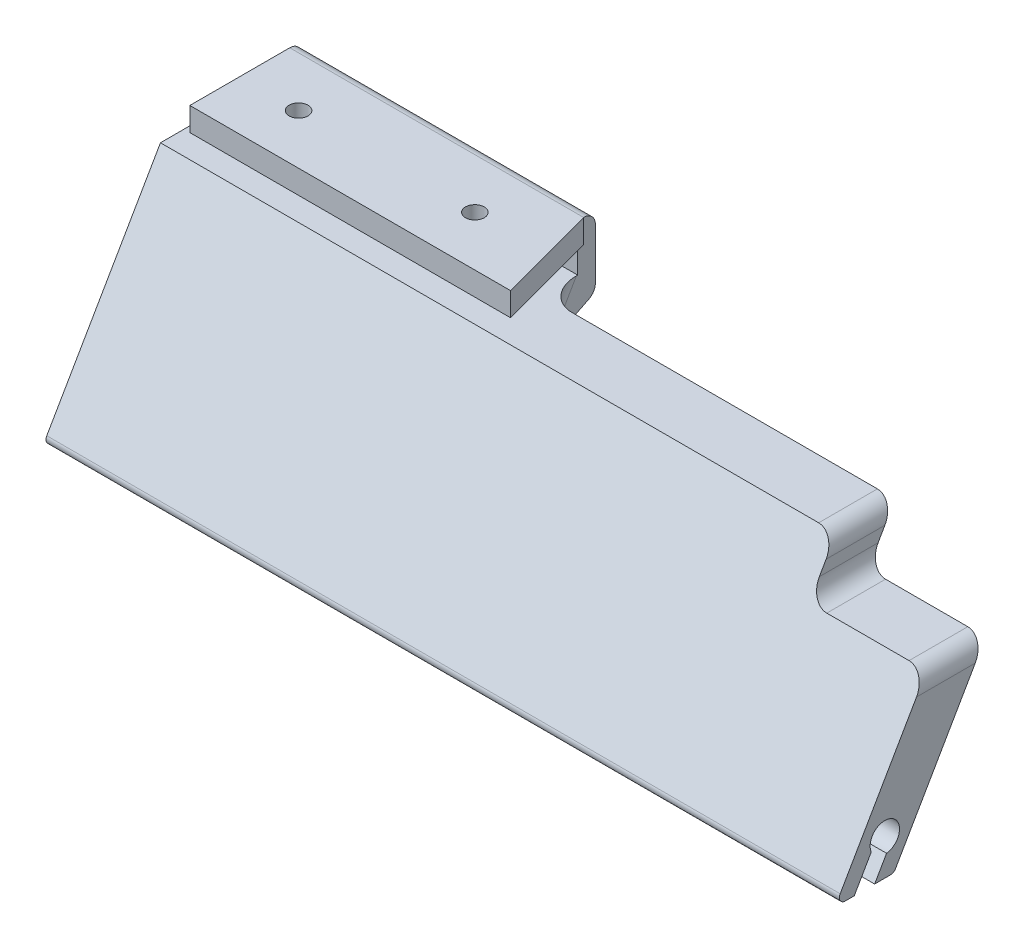
SolidWorks part; units mm, degrees
ref_plane "Front Plane" through (0, 0, 0) normal (0, 0, 1) x (1, 0, 0)
ref_plane "Top Plane" through (0, 0, 0) normal (0, 1, 0) x (1, 0, 0)
ref_plane "Right Plane" through (0, 0, 0) normal (1, 0, 0) x (0, 0, -1)
sketch "Sketch2" plane through (0, 0, 0) normal (1, 0, 0) x (0, 0, -1)
  line L0 (0, 0) -> (20.2073, 35)
  line L1 (20.2073, 35) -> (30.2073, 35)
  line L2 (30.2073, 35) -> (10, 0)
  line L3 (10, 0) -> (0, 0)
  line L4 (0, 0) -> (0, 35) construction
  line L5 (25.2073, 35) -> (5, 0) construction
  line L6 (3.2679, 0) -> (7.1651, 6.75)
  line L7 (7.1651, 6.75) -> (9.7631, 5.25)
  line L8 (9.7631, 5.25) -> (6.7321, 0)
  line L34 (20.2073, 35) -> (39.2073, 35)
  line L35 (20.2073, 35) -> (20.2073, 31)
  line L36 (20.2073, 31) -> (39.2073, 31)
  line L37 (39.2073, 35) -> (39.2073, 31)
  line L38 (39.2073, 35) -> (36.2073, 35)
  line L39 (39.2073, 35) -> (39.2073, 39)
  line L40 (39.2073, 39) -> (36.2073, 39)
  line L41 (36.2073, 35) -> (36.2073, 39)
  line L42 (39.2073, 39) -> (20.2073, 39)
  line L43 (39.2073, 39) -> (39.2073, 43)
  line L44 (39.2073, 43) -> (20.2073, 43)
  line L45 (20.2073, 39) -> (20.2073, 43)
  circle A0 centre (8.4641, 6) radius 2.5
  point P14 (8.4641, 6)
  dimension "D5" = 5
  dimension "D1" = 30
  dimension "D2" = 10
  dimension "D3" = 35
  dimension "D4" = 3
  dimension "D6" = 6
  dimension "D7" = 4
  dimension "D8" = 4
  dimension "D9" = 3
  dimension "D10" = 6
extrude "Boss-Extrude2" add sketch "Sketch2" along normal blind 50 contours L45 L42 L40 L43 L44 | L41 L34 L39 L40 | L37 L34 L2 L36 | L35 L36 L2 L1 | A0 L8 L3 L2 L36 L35 L0 L6 region at (0, 17.0999, -14.8085) region at (0, 33.087, -24.655) region at (0, 32.9242, -34.108) region at (0, 37, -37.7073) region at (0, 41, -29.7073)
sketch "Sketch3" plane through (50, 0, 0) normal (1, 0, 0) x (0, 0, -1)
  line L0 (0, 0) -> (20.2073, 35)
  line L2 (20.2073, 35) -> (30.2073, 35)
  line L3 (30.2073, 35) -> (10, 0)
  line L4 (10, 0) -> (6.7321, 0)
  line L5 (6.7321, 0) -> (8.7631, 3.5179)
  line L6 (8.7631, 3.5179) -> (6.1651, 5.0179)
  line L7 (6.1651, 5.0179) -> (3.2679, 0)
  line L8 (3.2679, 0) -> (0, 0)
  line L9 (20.2073, 35) -> (36.2073, 35) construction
  line L10 (0, 0) -> (20.2073, 35) construction
  circle A0 centre (8.4641, 6) radius 2.5
  arc A1 (8.7631, 3.5179) -> (6.1651, 5.0179) centre (8.4641, 6) ccw construction
  line M14 (20.2073, 35) -> (0, 0)
  line M15 (0, 0) -> (3.2679, 0)
  line M16 (3.2679, 0) -> (6.1651, 5.0179)
  arc M17 (6.1651, 5.0179) -> (8.7631, 3.5179) centre (8.4641, 6) cw
  line M18 (8.7631, 3.5179) -> (6.7321, 0)
  line M19 (6.7321, 0) -> (10, 0)
  line M20 (10, 0) -> (27.8979, 31)
extrude "Boss-Extrude3" add sketch "Sketch3" along normal blind 5 and the other way blind 130 contours L2 M14 M15 M16 M17 M18 M19 M20 region at (50, 18.8865, -15.9088)
fillet "Fillet5" radius 50 1 edges at (25, 31, -27.8979)
fillet "Fillet6" radius 5 2 edges at (0, 22.5778, -23.0353) (50, 22.5778, -23.0353)
fillet "Fillet7" radius 2 2 edges at (25, 43, -39.2073) (25, 31, -39.2073)
fillet "Fillet8" radius 1 2 edges at (-12.5, 0, -10) (-12.5, 0, 0)
ref_plane "Plane1" through (-80, 0, 0) normal (-1, 0, 0) x (0, 0, 1)
mirror "Mirror6" about plane through (-80, 0, 0) normal (-1, 0, 0) of bodies 103
sketch "Sketch4" plane through (0, 0, 0) normal (0, 1, 0) x (1, 0, 0)
  line L0 (-80, 55) -> (-80, -55) construction
  line L1 (-80, 0.7321) -> (55, 0.7321)
  line L2 (-80, 0.7321) -> (-80, 39.2073)
  line L3 (-80, 39.2073) -> (55, 39.2073)
  line L4 (55, 0.7321) -> (55, 39.2073)
  line L5 (55, 20.2073) -> (55, 0.866) construction
  line L7 (-215, 0.7321) -> (55, 0.7321) construction
  line L8 (0, 39.2073) -> (50, 39.2073) construction
extrude "Cut-Extrude2" cut sketch "Sketch4" along normal through all
sketch "Sketch5" plane through (0, 43, 0) normal (0, 1, 0) x (1, 0, 0)
  line L0 (-160, 37.2073) -> (-155.4449, 20.2073)
  line L1 (-155.4449, 20.2073) -> (-160, 20.2073)
  line L2 (-160, 20.2073) -> (-160, 37.2073)
  line L3 (-210, 20.2073) -> (-160, 20.2073) construction
  dimension "D1" = 15
extrude "Boss-Extrude4" add sketch "Sketch5" against normal up to surface (4 mm away)
sketch "Sketch6" plane through (0, 43, 0) normal (0, 1, 0) x (1, 0, 0)
  line L0 (-210, 28.7073) -> (-157.7224, 28.7073) construction
  line L1 (-210, 37.2073) -> (-210, 20.2073) construction
  line L2 (-155.4449, 20.2073) -> (-160, 37.2073) construction
  circle A0 centre (-200, 28.7073) radius 1.6
  circle A1 centre (-170, 28.7073) radius 1.6
  dimension "D1" = 3.2
  dimension "D3" = 10
  dimension "D2" = 10
extrude "Cut-Extrude3" cut sketch "Sketch6" against normal through all
ref_plane "Plane2" through (0, 32, 0) normal (0, 1, 0) x (1, 0, 0)
sketch "Sketch7" plane through (0, 32, 0) normal (0, 1, 0) x (1, 0, 0)
  circle A0 centre (-200, 28.7073) radius 3.5
  circle A1 centre (-170, 28.7073) radius 3.5
  dimension "D1" = 7
extrude "Cut-Extrude4" cut sketch "Sketch7" against normal through all
sketch "Sketch8" plane through (0, 0, -39.2073) normal (0, 0, -1) x (-1, 0, 0)
  line L1 (80, 35) -> (100, 35)
  line L2 (80, 35) -> (80, 27)
  line L3 (80, 27) -> (100, 27)
  line L4 (100, 35) -> (100, 27)
  dimension "D1" = 20
  dimension "D2" = 8
extrude "Cut-Extrude5" cut sketch "Sketch8" against normal through all
fillet "Fillet9" radius 3 3 edges at (-80, 27, -20.5885) (-100, 27, -20.5885) (-100, 35, -25.2073)
